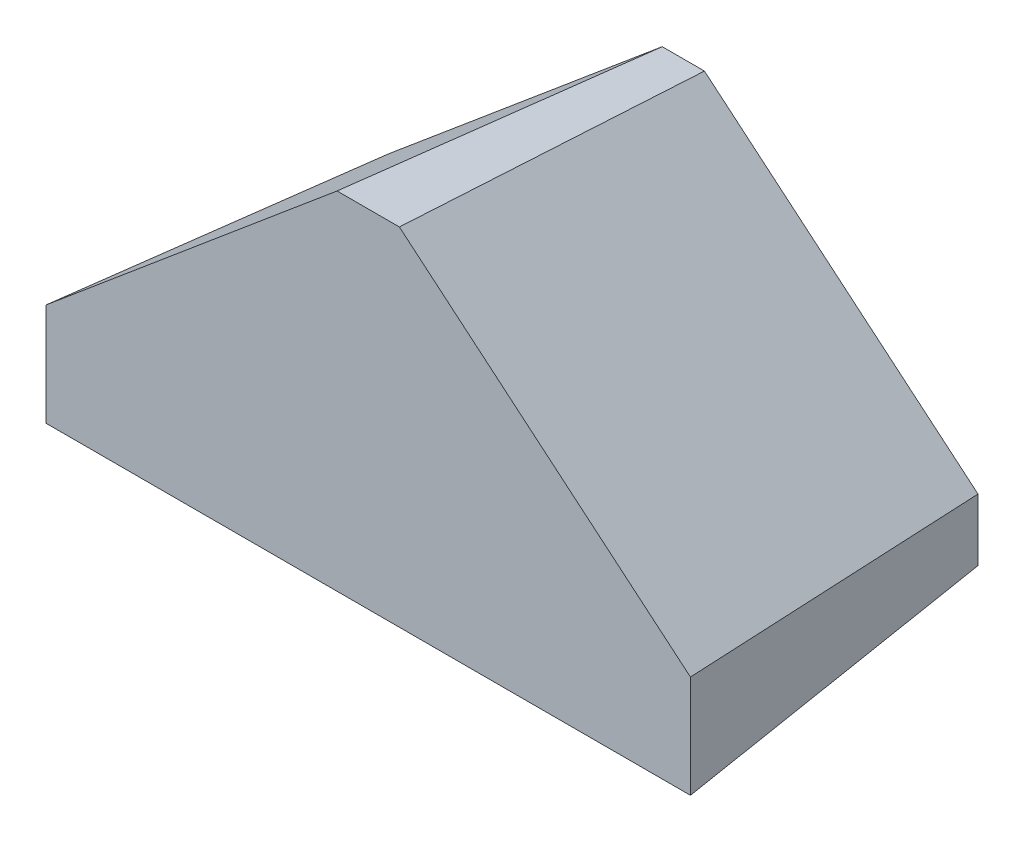
SolidWorks part; units mm, degrees
ref_plane "Alzado" through (0, 0, 0) normal (0, 0, 1) x (1, 0, 0)
ref_plane "Planta" through (0, 0, 0) normal (0, 1, 0) x (1, 0, 0)
ref_plane "Vista lateral" through (0, 0, 0) normal (1, 0, 0) x (0, 0, -1)
sketch "Croquis6" plane through (0, 0, 0) normal (0, 0, 1) x (1, 0, 0)
  line L1 (0, 0) -> (0, 10)
  line L2 (0, 10) -> (44.0949, 47)
  line L3 (44.0949, 47) -> (50.9051, 47)
  line L4 (50.9051, 47) -> (95, 10)
  line L5 (95, 10) -> (95, 0)
  line L7 (0, 10) -> (0.1282, 10) construction
  line L8 (95, 10) -> (119.0311, 10) construction
  line L9 (0, 0) -> (95, 0)
  point P0 (45.2299, 51.7763)
  dimension "D1" = 95
  dimension "D2" = 10
  dimension "D3" = 40
  dimension "D4" = 40
  dimension "D5" = 47
extrude "Saliente-Extruir3" add sketch "Croquis6" along normal blind 50.8 draft 5 draft outward yes
